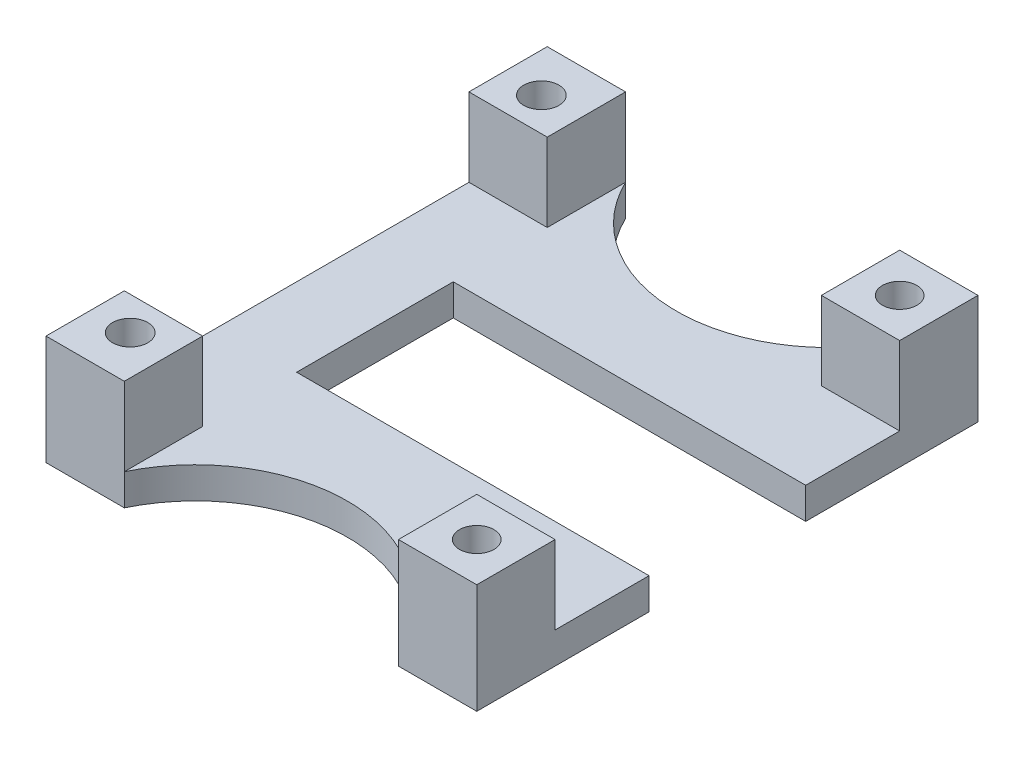
SolidWorks part; units mm, degrees
ref_plane "Front Plane" through (0, 0, 0) normal (0, 0, 1) x (1, 0, 0)
ref_plane "Top Plane" through (0, 0, 0) normal (0, 1, 0) x (1, 0, 0)
ref_plane "Right Plane" through (0, 0, 0) normal (1, 0, 0) x (0, 0, -1)
sketch "Sketch1" plane through (0, 0, 0) normal (0, 1, 0) x (1, 0, 0)
  line L0 (10, 10) -> (10, -10)
  line L1 (0, -20) -> (55, -20)
  line L2 (0, -20) -> (0, 20)
  line L3 (0, 20) -> (55, 20)
  line L4 (55, -20) -> (55, 20) construction
  line L5 (10, -10) -> (45, -10)
  line L6 (45, -10) -> (45, 10) construction
  line L7 (45, 10) -> (10, 10)
  line L8 (45, 10) -> (55, 10)
  line L11 (55, 10) -> (55, 20)
  line L13 (27.5, -20) -> (27.5, -10) construction
  line L14 (27.5, 10) -> (27.5, 20) construction
  line L16 (45, -10) -> (55, -10)
  line L17 (55, -20) -> (55, -10)
  line L18 (55, -20) -> (55, -32)
  line L19 (55, -32) -> (45, -32)
  line L20 (45, -32) -> (45, -20) construction
  line L21 (55, 20) -> (55, 32)
  line L22 (55, 32) -> (45, 32)
  line L23 (45, 32) -> (45, 20) construction
  line L24 (0, -20) -> (0, -32)
  line L25 (0, -32) -> (10, -32)
  line L26 (10, -32) -> (10, -20) construction
  line L27 (0, 20) -> (0, 32)
  line L28 (0, 32) -> (10, 32)
  line L29 (10, 32) -> (10, 20) construction
  line L30 (-7.7, 0) -> (7.7, 0) construction
  line L31 (0, 0) -> (55, 0) construction
  arc A26 (45, -32) -> (10, -32) centre (27.5, -40.4205) ccw
  arc A27 (10, 32) -> (45, 32) centre (27.5, 40.4205) ccw
  circle A46 centre (50, 27) radius 2.2
  circle A47 centre (50, -27) radius 2.2
  circle A49 centre (5, -26.25) radius 2.2479 construction
  circle A50 centre (5, -26.25) radius 2.2479
  circle A51 centre (5, 26.25) radius 2.2479 construction
  circle A52 centre (5, 26.25) radius 2.2479
  point P33 (27.5, 21)
  point P34 (27.5, -21)
  point P39 (0, 0)
  dimension "D18" = 4.4
  dimension "D19" = 4.4
  dimension "D1" = 40
  dimension "D2" = 55
  dimension "D3" = 10
  dimension "D22" = 10
  dimension "D23" = 10
  dimension "D24" = 10
  dimension "D13" = 5
  dimension "D16" = 5
  dimension "D7" = 10
  dimension "D10" = 12
  dimension "D11" = 12
  dimension "D12" = 10
  dimension "D9" = 5
  dimension "D14" = 5
  dimension "D15" = 12
  dimension "D17" = 10
  dimension "D20" = 10
  dimension "D21" = 12
  dimension "D27" = 1
  dimension "D28" = 1
extrude "Extrude-Body" add sketch "Sketch1" along normal blind 4 contours L1 L4 L3 L2 A47 A46 L7 L6 L5 L0 | L20 L19 L18 L1 A47 | L22 L23 L3 L21 A46 | L29 L28 L27 L3 | L25 L26 L1 L24 region at (9.3199, 0, 0) region at (27.5, 0, -20.5629) region at (54.4371, 0, 26)
sketch "Sketch5" plane through (0, 4, 0) normal (0, 1, 0) x (1, 0, 0)
  line L9 (45, -22) -> (55, -22)
  line L21 (55, -22) -> (55, -32)
  line L36 (55, -32) -> (45, -32)
  line L37 (45, -32) -> (45, -22)
  line L38 (55, 22) -> (55, 32)
  line L39 (55, 32) -> (45, 32)
  line L41 (45, 32) -> (45, 22)
  line L42 (45, 22) -> (55, 22)
  line L43 (10, 22) -> (10, 32)
  line L44 (10, 32) -> (0, 32)
  line L46 (0, 32) -> (0, 22)
  line L47 (0, -32) -> (0, 32) construction
  line L48 (0, 22) -> (10, 22)
  line L49 (10, -22) -> (0, -22)
  line L50 (0, -22) -> (0, -32)
  line L51 (0, -32) -> (10, -32)
  line L52 (10, -32) -> (10, -22)
  circle A0 centre (50, 27) radius 2.2
  circle A3 centre (50, -27) radius 2.2
  circle A11 centre (50, 27) radius 2.2 construction
  circle A12 centre (50, -27) radius 2.2 construction
  circle A13 centre (5, 26.25) radius 2.2479 construction
  circle A14 centre (5, 26.25) radius 2.2479
  circle A15 centre (5, -26.25) radius 2.2479 construction
  circle A16 centre (5, -26.25) radius 2.2479
  dimension "D1" = 10
  dimension "D2" = 10
  dimension "D3" = 10
  dimension "D4" = 10
  dimension "D5" = 10
  dimension "D6" = 10
  dimension "D7" = 10
  dimension "D8" = 10
extrude "Extrude-Legs" add sketch "Sketch5" along normal blind 10
equation "\"boltdiameter\"=4.4"
equation "\"D18@Sketch1\"=\"boltdiameter\""
equation "\"D19@Sketch1\"=\"boltdiameter\""
equation "\"boltfacediameter\"=7"
equation "\"insetNutFlat\"=8.4"
equation "\"screwInset\"=8.43"
equation "\"slotLength\"=80"
